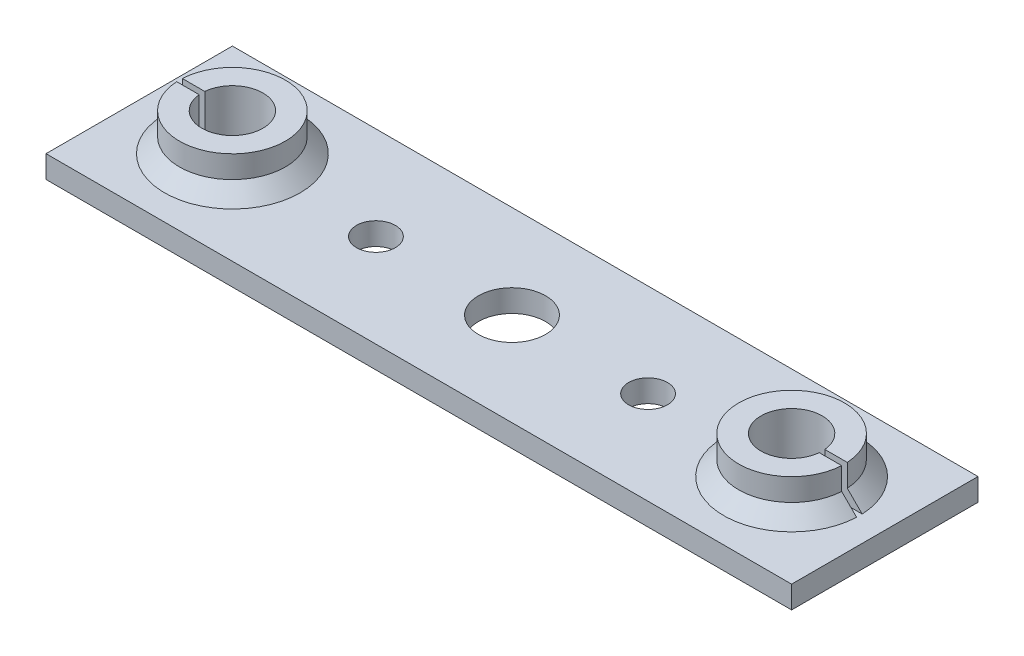
SolidWorks part; units mm, degrees
ref_plane "Front Plane" through (0, 0, 0) normal (0, 0, 1) x (1, 0, 0)
ref_plane "Top Plane" through (0, 0, 0) normal (0, 1, 0) x (1, 0, 0)
ref_plane "Right Plane" through (0, 0, 0) normal (1, 0, 0) x (0, 0, -1)
sketch "Sketch1" plane through (0, 0, 0) normal (0, 1, 0) x (1, 0, 0)
  line L0 (0, 18.2751) -> (0, -23.7638) construction
  line L1 (-40.7915, 0) -> (38.5461, 0) construction
  line L3 (50, -12.5) -> (-50, -12.5)
  line L4 (50, -12.5) -> (50, 12.5)
  line L5 (50, 12.5) -> (-50, 12.5)
  line L6 (-50, -12.5) -> (-50, 12.5)
  line L7 (50, -12.5) -> (-50, 12.5) construction
  line L8 (50, 12.5) -> (-50, -12.5) construction
  circle A0 centre (-37.5, 0) radius 4.1
  circle A1 centre (37.5, 0) radius 4.1
  circle A2 centre (-18.25, 0) radius 2.6
  circle A3 centre (18.25, 0) radius 2.6
  circle A4 centre (0, 0) radius 4.5
  point P7 (0, 0)
  dimension "D1" = 8.2
  dimension "D2" = 75
  dimension "D5" = 5.2
  dimension "D6" = 36.5
  dimension "D7" = 9
  dimension "D3" = 25
  dimension "D4" = 100
extrude "Boss-Extrude1" add sketch "Sketch1" along normal blind 3
sketch "Sketch2" plane through (0, 3, 0) normal (0, 1, 0) x (1, 0, 0)
  line L0 (0, 12.5) -> (0, -12.5) construction
  line L1 (50, 12.5) -> (-50, 12.5) construction
  line L2 (-50, -12.5) -> (50, -12.5) construction
  line L3 (-37.5, 0) -> (-44.6, 0) construction
  line L4 (-41.5828, 0.375) -> (-44.5901, 0.375)
  line L5 (-41.5828, -0.375) -> (-44.5901, -0.375)
  line L6 (41.5828, -0.375) -> (44.5901, -0.375)
  line L7 (41.5828, 0.375) -> (44.5901, 0.375)
  circle A0 centre (-37.5, 0) radius 4.1
  circle A1 centre (-37.5, 0) radius 7.1
  circle A2 centre (37.5, 0) radius 4.1
  circle A3 centre (37.5, 0) radius 7.1
  circle M6 centre (-37.5, 0) radius 4.1
  circle M11 centre (37.5, 0) radius 4.1
  dimension "D1" = 8.2
  dimension "D2" = 3
  dimension "D3" = 0.75
extrude "Boss-Extrude2" add sketch "Sketch2" along normal blind 5 contours L5 A1 L4 M6 | A3 L6 L7 M11 region at (-43.0865, 3, -0.5757) region at (43.0865, 3, 0.5757)
chamfer "Chamfer1" distance 2 angle 45 2 edges at (30.4, 3, 0) (-30.4, 3, 0)
